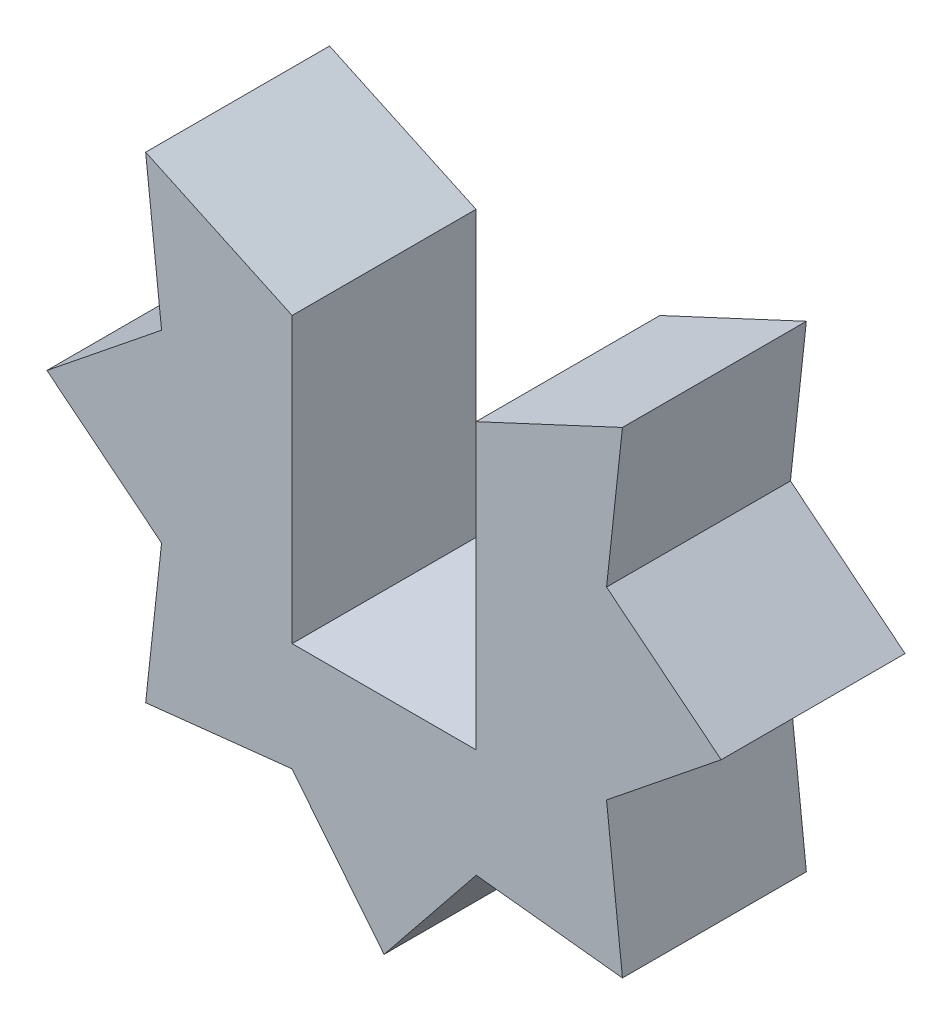
SolidWorks part; units mm, degrees
ref_plane "Plano frontal" through (0, 0, 0) normal (0, 0, 1) x (1, 0, 0)
ref_plane "Plano superior" through (0, 0, 0) normal (0, 1, 0) x (1, 0, 0)
ref_plane "Plano direito" through (0, 0, 0) normal (1, 0, 0) x (0, 0, -1)
sketch "Esboço1" plane through (0, 0, 0) normal (0, 0, 1) x (1, 0, 0)
  line L4 (-3, 2.2809) -> (3, 2.2809)
  line L5 (-11, 0) -> (11, 0) construction
  line L6 (0, 0) -> (0, -11) construction
  line L7 (-7.7782, 7.7782) -> (7.7782, -7.7782) construction
  line L8 (-7.7782, -7.7782) -> (7.7782, 7.7782) construction
  line L13 (-10.1627, -4.2095) -> (10.1627, 4.2095) construction
  line L25 (-10.1627, 4.2095) -> (10.1627, -4.2095) construction
  line L26 (-7.259, 3.0068) -> (-11, 0)
  line L27 (-11, 0) -> (-7.2591, -3.0068)
  line L29 (-7.7782, 7.7782) -> (-7.259, 3.0068)
  line L32 (7.259, 3.0068) -> (7.7782, 7.7782)
  line L34 (7.259, -3.0068) -> (11, 0)
  line L35 (11, 0) -> (7.259, 3.0068)
  line L36 (3.0068, -7.259) -> (7.7782, -7.7782)
  line L37 (7.7782, -7.7782) -> (7.259, -3.0068)
  line L38 (-3.0068, -7.259) -> (0, -11)
  line L39 (0, -11) -> (3.0068, -7.259)
  line L40 (-7.2591, -3.0068) -> (-7.7782, -7.7782)
  line L41 (-7.7782, -7.7782) -> (-3.0068, -7.259)
  line L42 (-3, 5.5527) -> (-7.7782, 7.7782)
  line L43 (3, 5.5527) -> (7.7782, 7.7782)
  line L44 (-3, 5.5527) -> (-3, 2.2809)
  line L45 (3, 5.5527) -> (3, 2.2809)
  arc A3 (-7.7782, 7.7782) -> (7.7782, 7.7782) centre (0, 0) ccw
  arc A4 (-4.6601, 6.3259) -> (4.6601, 6.3259) centre (0, 0) ccw
  dimension "D2" = 3.2719
  dimension "D13" = 24.974
  dimension "D4" = 7.8571
  dimension "D10" = 11
  dimension "D3" = 6
  dimension "D5" = 45
  dimension "D6" = 22.5
  dimension "D8" = 22.5
  dimension "D11" = 77.581
  dimension "D12" = 90
extrude "Ressalto-extrusão1" add sketch "Esboço1" along normal blind 6 contours A4 L43 L45 L4 L44 L42 | A4 L32 L43 | A4 L34 L35 | A4 L36 L37 | A4 L38 L39 | A4 L40 L41 | A4 L26 L27 | A4 L42 L29 region at (0, -1.1325, 0) region at (-6.6328, 5.8292, 0) region at (6.6328, 5.8292, 0) region at (-8.7815, 0, 0) region at (8.7815, 0, 0) region at (-6.2095, -6.2095, 0) region at (6.2095, -6.2095, 0) region at (0, -8.7815, 0)
sketch "Esboço2" plane through (0, 0, 6) normal (0, 0, 1) x (1, 0, 0)
  line L0 (-3, 2.2809) -> (-3, -3.7191)
  line L1 (3, 2.2809) -> (3, -3.7191)
  line L2 (3, -3.7191) -> (-3, -3.7191)
  line L3 (-3, 2.2809) -> (3, 2.2809)
  dimension "D1" = 6
  dimension "D2" = 6
extrude "Corte-extrusão1" cut sketch "Esboço2" against normal blind 10
